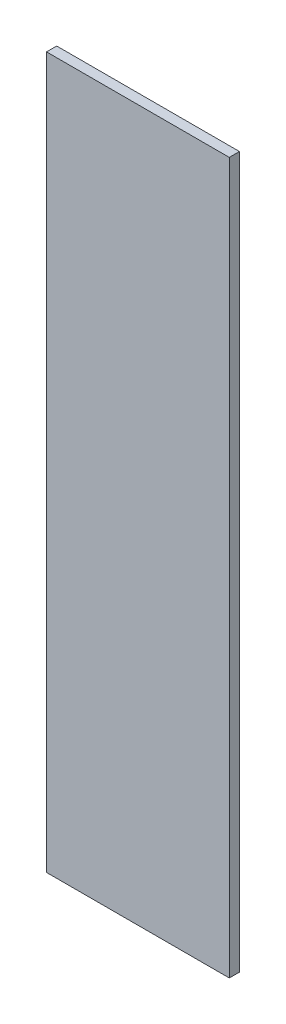
SolidWorks part; units mm, degrees
material "Oak"
ref_plane "Front Plane" through (0, 0, 0) normal (0, 0, 1) x (1, 0, 0)
ref_plane "Top Plane" through (0, 0, 0) normal (0, 1, 0) x (1, 0, 0)
ref_plane "Right Plane" through (0, 0, 0) normal (1, 0, 0) x (0, 0, -1)
sketch "Sketch1" plane through (0, 0, 0) normal (0, 0, 1) x (1, 0, 0)
  line L1 (-45, 175) -> (45, 175)
  line L2 (-45, 175) -> (-45, -175)
  line L3 (-45, -175) -> (45, -175)
  line L4 (45, 175) -> (45, -175)
  line L5 (-45, 175) -> (45, -175) construction
  line L6 (-45, -175) -> (45, 175) construction
  point P0 (0, 0)
  dimension "D1" = 90
  dimension "D2" = 350
base flange "Base-Flange1" sketch "Sketch1" thickness 5 reverse thickness direction no parameters "D1"=0.7366
sketch "Bend-Lines1" [suppressed] plane through (0, 0, 0) normal (0, 1, 0) x (1, 0, 0)
sketch "Bounding-Box1" [suppressed] plane through (0, 0, 0) normal (0, 1, 0) x (1, 0, 0)
sheet metal parameters "Sheet-Metal1" thickness 5 parameters "D1"=0.7366
flat pattern "Flat-Pattern1" [suppressed]
sketch "Bend-Lines2" plane through (0, 0, 0) normal (0, 1, 0) x (1, 0, 0)
sketch3d "Bounding-Box2" [suppressed]
  line L0 (-45, 175, 0) -> (-45, -175, 0) construction
  line L1 (45, 175, 0) -> (45, -175, 0) construction
  line L2 (-45, 175, 0) -> (45, 175, 0) construction
  line L3 (-45, -175, 0) -> (45, -175, 0) construction
